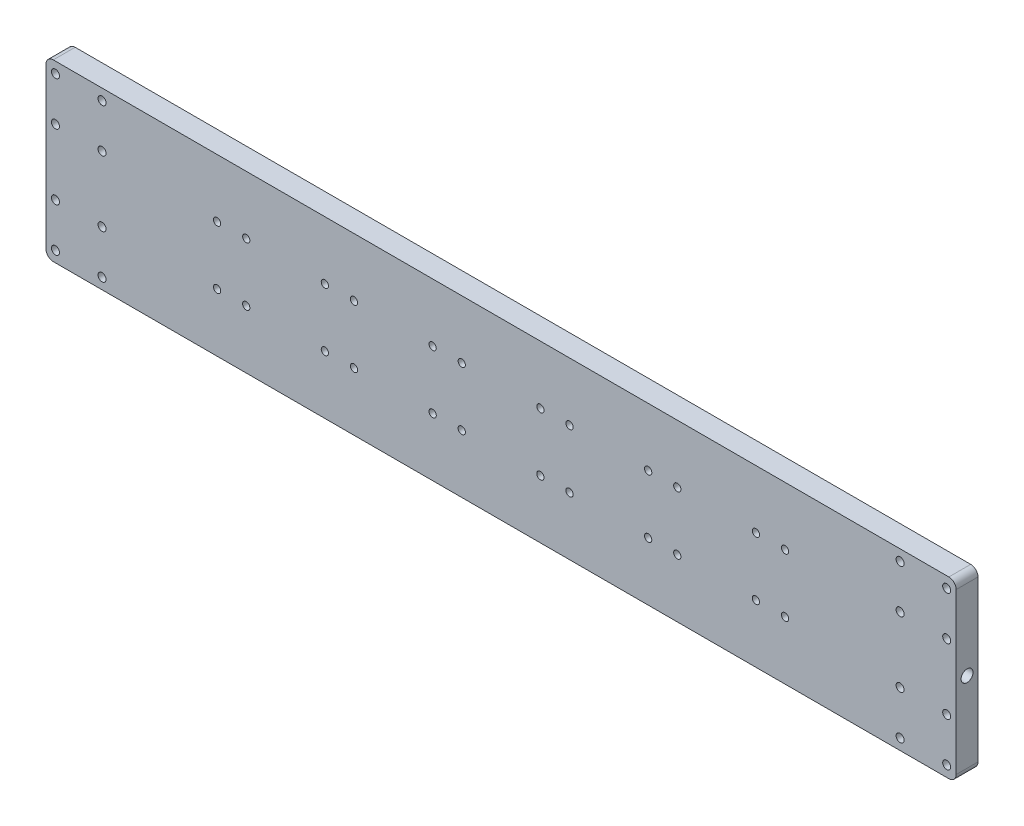
SolidWorks part; units mm, degrees
ref_plane "Plan de face" through (0, 0, 0) normal (0, 0, 1) x (1, 0, 0)
ref_plane "Plan de dessus" through (0, 0, 0) normal (0, 1, 0) x (1, 0, 0)
ref_plane "Plan de droite" through (0, 0, 0) normal (1, 0, 0) x (0, 0, -1)
sketch "Esquisse1" plane through (0, 0, 0) normal (0, 0, 1) x (1, 0, 0)
  line L1 (0, 0) -> (625, 0)
  line L2 (0, 0) -> (0, 120)
  line L3 (0, 120) -> (625, 120)
  line L4 (625, 0) -> (625, 120)
  dimension "D1" = 120
  dimension "D2" = 625
extrude "Boss.-Extru.1" add sketch "Esquisse1" along normal blind 15
sketch "Esquisse2" plane through (0, 0, 15) normal (0, 0, 1) x (1, 0, 0)
  line L0 (312.5, 0) -> (312.5, 120) construction
  line L1 (0, 0) -> (625, 0) construction
  line L2 (625, 120) -> (0, 120) construction
  line L3 (22.5, 120) -> (22.5, 0) construction
  line L4 (22.5, 60) -> (0, 60) construction
  line L5 (0, 120) -> (0, 0) construction
  line L6 (6.5, 112.5) -> (6.5, 82.5) construction
  line L7 (618.5, 112.5) -> (618.5, 82.5) construction
  line L8 (602.5, 60) -> (625, 60) construction
  line L9 (602.5, 120) -> (602.5, 0) construction
  circle A0 centre (6.5, 112.5) radius 2.75
  circle A1 centre (6.5, 82.5) radius 2.75
  circle A2 centre (38.5, 82.5) radius 2.75
  circle A3 centre (38.5, 112.5) radius 2.75
  circle A4 centre (38.5, 7.5) radius 2.75
  circle A5 centre (38.5, 37.5) radius 2.75
  circle A6 centre (6.5, 37.5) radius 2.75
  circle A7 centre (6.5, 7.5) radius 2.75
  circle A8 centre (618.5, 7.5) radius 2.75
  circle A9 centre (618.5, 37.5) radius 2.75
  circle A10 centre (586.5, 37.5) radius 2.75
  circle A11 centre (586.5, 7.5) radius 2.75
  circle A12 centre (586.5, 112.5) radius 2.75
  circle A13 centre (586.5, 82.5) radius 2.75
  circle A14 centre (618.5, 82.5) radius 2.75
  circle A15 centre (618.5, 112.5) radius 2.75
  dimension "D1" = 30
  dimension "D2" = 32
  dimension "D3" = 5.5
  dimension "D4" = 45
  dimension "D5" = 580
extrude "Enlèv. mat.-Extru.1" cut sketch "Esquisse2" against normal through all both and the other way through all
fillet "Congé1" radius 5 4 edges at (625, 120, 7.5) (625, 0, 7.5) (0, 0, 7.5) (0, 120, 7.5)
sketch "Esquisse3" plane through (625, 0, 0) normal (1, 0, 0) x (0, 0, -1)
  line L0 (-15, 60) -> (0, 60) construction
  line L1 (-15, 5) -> (-15, 115) construction
  line L2 (0, 5) -> (0, 115) construction
  circle A0 centre (-7.5, 60) radius 4.1
  dimension "D1" = 8.2
extrude "Enlèv. mat.-Extru.2" cut sketch "Esquisse3" against normal blind 20
extrude "Enlèv. mat.-Extru.3" cut sketch "Esquisse3<2>" along normal blind 20 from surface starting at face at (0, 60, 7.5)
sketch "Esquisse3<2>" plane through (625, 0, 0) normal (1, 0, 0) x (0, 0, -1) same geometry as "Esquisse3"
sketch "Esquisse4" plane through (0, 0, 15) normal (0, 0, 1) x (1, 0, 0)
  line L0 (0, 60) -> (625, 60) construction
  line L1 (0, 115) -> (0, 5) construction
  line L2 (625, 5) -> (625, 115) construction
  line L3 (312.5, 60) -> (312.5, 120) construction
  line L4 (620, 120) -> (5, 120) construction
  line L5 (275.5, 60) -> (275.5, 93.3675) construction
  line L6 (238.5, 60) -> (238.5, 112.952) construction
  line L7 (164.5, 60) -> (164.5, 101.3546) construction
  circle A0 centre (265.5, 80) radius 2.5
  circle A1 centre (285.5, 80) radius 2.5
  circle A2 centre (285.5, 40) radius 2.5
  circle A3 centre (265.5, 40) radius 2.5
  circle A4 centre (359.5, 40) radius 2.5
  circle A5 centre (339.5, 40) radius 2.5
  circle A6 centre (339.5, 80) radius 2.5
  circle A7 centre (359.5, 80) radius 2.5
  circle A8 centre (211.5, 40) radius 2.5
  circle A9 centre (191.5, 40) radius 2.5
  circle A10 centre (191.5, 80) radius 2.5
  circle A11 centre (211.5, 80) radius 2.5
  circle A12 centre (117.5, 80) radius 2.5
  circle A13 centre (137.5, 80) radius 2.5
  circle A14 centre (137.5, 40) radius 2.5
  circle A15 centre (117.5, 40) radius 2.5
  circle A16 centre (507.5, 40) radius 2.5
  circle A17 centre (487.5, 40) radius 2.5
  circle A18 centre (487.5, 80) radius 2.5
  circle A19 centre (507.5, 80) radius 2.5
  circle A20 centre (413.5, 80) radius 2.5
  circle A21 centre (433.5, 80) radius 2.5
  circle A22 centre (433.5, 40) radius 2.5
  circle A23 centre (413.5, 40) radius 2.5
  dimension "D1" = 5
  dimension "D2" = 20
  dimension "D3" = 40
  dimension "D4" = 37
  dimension "D5" = 74
  dimension "D6" = 74
extrude "Enlèv. mat.-Extru.4" cut sketch "Esquisse4" against normal through all both and the other way through all
